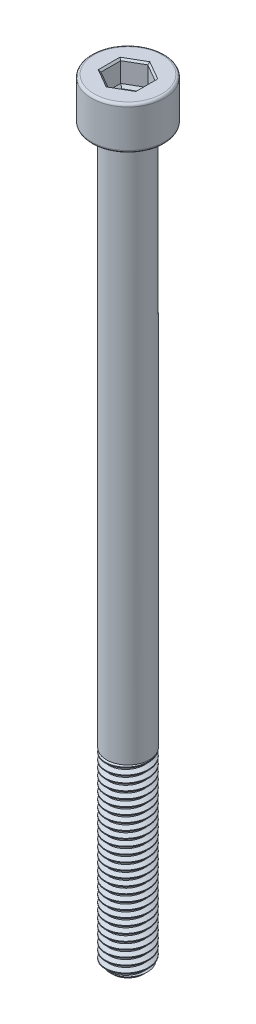
SolidWorks part; units mm, degrees
material "AISI Type A2 Tool Steel"
ref_plane "Front Plane" through (0, 0, 0) normal (0, 0, 1) x (1, 0, 0)
ref_plane "Top Plane" through (0, 0, 0) normal (0, 1, 0) x (1, 0, 0)
ref_plane "Right Plane" through (0, 0, 0) normal (1, 0, 0) x (0, 0, -1)
sketch "Sketch1" plane through (0, 0, 0) normal (0, 1, 0) x (1, 0, 0)
  circle A0 centre (0, 0) radius 2.5
  dimension "D1" = 5
extrude "Boss-Extrude1" add sketch "Sketch1" along normal blind 22
thread "Thread1" pitch 0.8 method cut profile "Thread Profile1" start angle 0, offset 1, length 0, pitch 0.8, diameter 5
ref_plane "Plane1" through (-2.5, 23, 0) normal (0, 0, 1) x (-1, 0, 0)
sketch "Thread Profile1" plane through (-2.5, 23, 0) normal (0, 0, 1) x (-1, 0, 0)
  line L0 (0, 0) -> (0, 0.8) construction
  line L11 (0, 0) -> (0, 0.7)
  line L12 (0, 0.7) -> (-0.433, 0.45)
  line L13 (-0.433, 0.45) -> (-0.433, 0.25)
  line L15 (-0.433, 0.25) -> (0, 0)
  line L17 (-0.433, 0.35) -> (0, 0.35) construction
  point P2 (0, 0)
  dimension "Pitch" = 0.8
  dimension "Profile_Angle" = 60
  dimension "Profile_Land" = 0.2
  dimension "Profile_Height" = 0.433
sketch "Sketch2" plane through (0, 22, 0) normal (0, 1, 0) x (1, 0, 0)
  circle A0 centre (0, 0) radius 2.5
  dimension "D1" = 5
extrude "Boss-Extrude2" add sketch "Sketch2" along normal blind 63
sketch "Sketch3" plane through (0, 85, 0) normal (0, 1, 0) x (1, 0, 0)
  circle A0 centre (0, 0) radius 4.25
  dimension "D1" = 8.5
extrude "Boss-Extrude3" add sketch "Sketch3" along normal blind 5
fillet "Fillet1" radius 0.3 2 edges at (0, 85, 4.25) (0, 90, 4.25)
sketch "Sketch4" plane through (0, 0, 0) normal (0, 0, 1) x (1, 0, 0)
  line L0 (0, 0) -> (0, 0.4416) construction
  line L1 (0, 0) -> (2.51, 0) construction
  line L2 (2.51, 0) -> (2.51, 0.7)
  line L3 (2.51, 0.7) -> (1.81, 0)
  line L4 (1.81, 0) -> (2.51, 0)
  dimension "D1" = 0.7
  dimension "D2" = 45
  dimension "D3" = 2.51
revolve "Cut-Revolve1" cut sketch "Sketch4" angle 360 about L0
sketch "Sketch5" plane through (0, 90, 0) normal (0, 1, 0) x (1, 0, 0)
  line L1 (0, 2.3094) -> (-2, 1.1547)
  line L2 (-2, 1.1547) -> (-2, -1.1547)
  line L3 (-2, -1.1547) -> (0, -2.3094)
  line L4 (0, -2.3094) -> (2, -1.1547)
  line L5 (2, -1.1547) -> (2, 1.1547)
  line L6 (2, 1.1547) -> (0, 2.3094)
  circle A0 centre (0, 0) radius 2 construction
  dimension "D1" = 4
extrude "Cut-Extrude1" cut sketch "Sketch5" against normal blind 2.5
chamfer "Chamfer1" distance 0.2 angle 45 6 edges at (-1, 90, 1.7321) (1, 90, 1.7321) (2, 90, 0) (1, 90, -1.7321) (-1, 90, -1.7321) (-2, 90, 0)
sketch "Sketch6" plane through (0, 87.5, 0) normal (0, 1, 0) x (1, 0, 0)
  line L1 (0, 2.3094) -> (-2, 1.1547)
  line L2 (-2, 1.1547) -> (-2, -1.1547)
  line L3 (-2, -1.1547) -> (0, -2.3094)
  line L4 (0, -2.3094) -> (2, -1.1547)
  line L5 (2, -1.1547) -> (2, 1.1547)
  line L6 (2, 1.1547) -> (0, 2.3094)
  circle A0 centre (0, 0) radius 2 construction
extrude "Cut-Extrude2" cut sketch "Sketch6" against normal blind 0.3 draft 45
